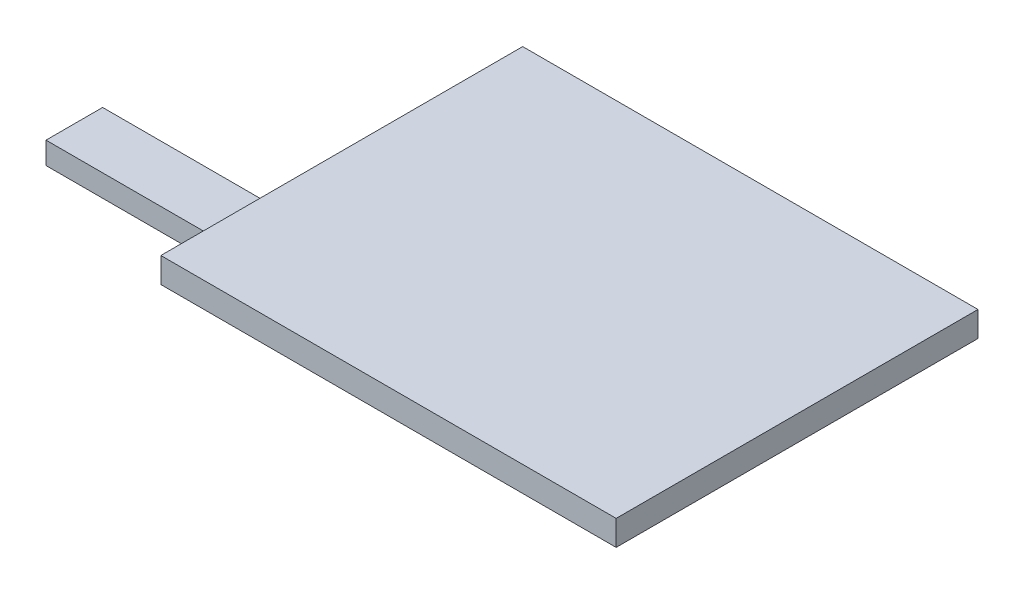
SolidWorks part; units mm, degrees
ref_plane "Front Plane" through (0, 0, 0) normal (0, 0, 1) x (1, 0, 0)
ref_plane "Top Plane" through (0, 0, 0) normal (0, 1, 0) x (1, 0, 0)
ref_plane "Right Plane" through (0, 0, 0) normal (1, 0, 0) x (0, 0, -1)
sketch "Sketch1" plane through (0, 0, 0) normal (0, 0, 1) x (1, 0, 0)
  line L0 (-37.4502, 11.0728) -> (107.2498, 11.0728)
  line L1 (107.2498, 11.0728) -> (107.2498, 3.0728)
  line L2 (107.2498, 3.0728) -> (-37.4502, 3.0728)
  line L3 (-37.4502, 3.0728) -> (-37.4502, 11.0728)
  dimension "D1" = 8
  dimension "D2" = 144.7
extrude "Boss-Extrude1" add sketch "Sketch1" along normal blind 115
sketch "Sketch2" plane through (0, 11.0728, 0) normal (0, 1, 0) x (1, 0, 0)
  line L0 (-37.4502, -57.5) -> (107.2498, -57.5) construction
  line L1 (-37.4502, -115) -> (-37.4502, 0) construction
  line L2 (107.2498, -115) -> (107.2498, 0) construction
sketch "Sketch3" plane through (0, 3.0728, 0) normal (0, -1, 0) x (1, 0, 0)
  line L0 (-37.4502, 77.5) -> (-10.4789, 77.5) construction
  line L1 (-37.4502, 115) -> (-37.4502, 0) construction
  line L2 (-37.4502, 57.5) -> (107.2498, 57.5) construction
  line L3 (-37.4502, 86.5) -> (-27.4502, 86.5)
  line L4 (-27.4502, 86.5) -> (-27.4502, 68.5)
  line L5 (-27.4502, 68.5) -> (-37.4502, 68.5)
  line L6 (-37.4502, 68.5) -> (-37.4502, 86.5)
  dimension "D1" = 20
  dimension "D2" = 10
  dimension "D3" = 9
  dimension "D4" = 9
extrude "Boss-Extrude2" add sketch "Sketch3" along normal blind 14
sketch "Sketch4" plane through (-37.4502, 0, 0) normal (-1, 0, 0) x (0, 0, 1)
  line L0 (68.5, -10.9272) -> (68.5, -3.9272)
  line L1 (68.5, -10.9272) -> (68.5, 3.0728) construction
  line L2 (68.5, -3.9272) -> (86.5, -3.9272)
  line L3 (86.5, -10.9272) -> (86.5, 3.0728) construction
  line L4 (86.5, -3.9272) -> (86.5, -10.9272)
  line L5 (86.5, -10.9272) -> (68.5, -10.9272)
  dimension "D1" = 7
extrude "Boss-Extrude6" add sketch "Sketch4" along normal blind 65
ref_plane "Plane1" through (-27.4502, 0, 0) normal (1, 0, 0) x (0, 1, 0)
sketch "Sketch7" plane through (-27.4502, 0, 0) normal (1, 0, 0) x (0, 1, 0)
  line L0 (3.0728, 86.5) -> (3.0728, 98.5)
  line L1 (3.0728, 68.5) -> (3.0728, 56.5)
  line L2 (-10.9272, 68.5) -> (3.0728, 68.5)
  line L3 (3.0728, 86.5) -> (-10.9272, 86.5)
  arc A0 (3.0728, 98.5) -> (-10.9272, 86.5) centre (7.6232, 79.0245) ccw
  arc A1 (3.0728, 56.5) -> (-10.9272, 68.5) centre (7.6232, 75.9755) cw
  dimension "D2" = 20
  dimension "D4" = 20
  dimension "D1" = 12
  dimension "D3" = 12
extrude "Boss-Extrude9" add sketch "Sketch7" against normal blind 10
